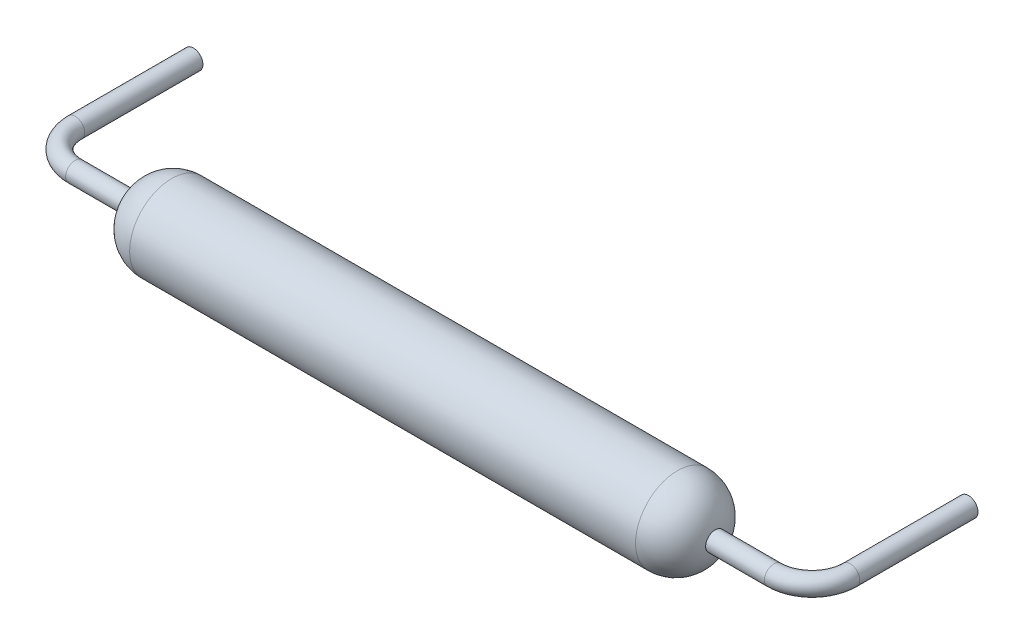
SolidWorks part; units mm, degrees
ref_plane "Front Plane" through (0, 0, 0) normal (0, 0, 1) x (1, 0, 0)
ref_plane "Top Plane" through (0, 0, 0) normal (0, 1, 0) x (1, 0, 0)
ref_plane "Right Plane" through (0, 0, 0) normal (1, 0, 0) x (0, 0, -1)
sketch "Sketch1" plane through (0, 0, 0) normal (1, 0, 0) x (0, 0, -1)
  circle A0 centre (-1.1, 0) radius 1.1
  dimension "D1" = 2.2
extrude "Extrude1" add sketch "Sketch1" along normal blind 7.62 from offset 2.54
sketch "Sketch2" plane through (0, 0, 0) normal (0, 1, 0) x (1, 0, 0)
  line L0 (2.54, -1.1) -> (1, -1.1)
  line L1 (2.54, 0) -> (2.54, -2.2) construction
  line L2 (0, -0.1) -> (0, 3)
  arc A0 (1, -1.1) -> (0, -0.1) centre (1, -0.1) cw
  dimension "D2" = 1
  dimension "D1" = 3
sketch "Sketch3" plane through (2.54, 0, 0) normal (-1, 0, 0) x (0, 0, 1)
  line L0 (1.1, 0) -> (0.1, 0) construction
  circle A0 centre (1.1, 0) radius 0.25
  dimension "D1" = 0.5
sweep "Sweep1" add profiles "Sketch3" path "Sketch2"
fillet "Fillet1" radius 1 1 edges at (2.54, 0, 0)
mirror "Mirror1" about plane through (10.16, 0, 1.1) normal (1, 0, 0) of bodies 102
